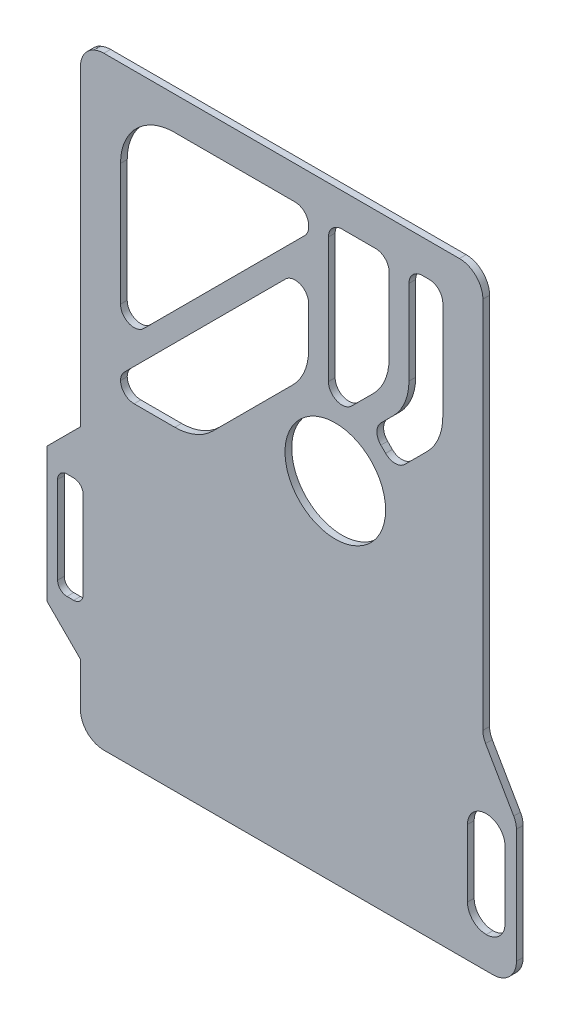
SolidWorks part; units mm, degrees
ref_plane "前视基准面" through (0, 0, 0) normal (0, 0, 1) x (1, 0, 0)
ref_plane "上视基准面" through (0, 0, 0) normal (0, 1, 0) x (1, 0, 0)
ref_plane "右视基准面" through (0, 0, 0) normal (1, 0, 0) x (0, 0, -1)
sketch "草图1" plane through (0, 0, 0) normal (0, 0, 1) x (1, 0, 0)
  line L27 (-1, -50) -> (-1.032, -50)
  line L28 (-34, 37.6372) -> (-34, 37.6623)
  line L29 (-36, 34.5) -> (-36, -12)
  line L30 (-36, -12) -> (-41, -17)
  line L31 (-41, -17) -> (-41, -37)
  line L32 (-41, -37) -> (-36, -42)
  line L33 (-36, -42) -> (-36, -48.5)
  line L34 (-32.5, -52) -> (-3, -52)
  line L35 (-38, -34.5) -> (-37, -34.5)
  line L36 (-36, -33.5) -> (-36, -20.5)
  line L37 (-37, -19.5) -> (-38, -19.5)
  line L38 (-39, -20.5) -> (-39, -33.5)
  line L40 (24, 37.9774) -> (-32.5, 37.9774)
  line L50 (12.9774, 31) -> (12.9774, 18.3848)
  line L51 (16, 33.0226) -> (15, 33.0226)
  line L52 (18.0226, 16.3137) -> (18.0226, 31)
  line L53 (12.3592, 7.3271) -> (15.6729, 10.6408)
  line L54 (8.7916, 8.0342) -> (9.4987, 7.3271)
  line L55 (10.6408, 12.7439) -> (8.7916, 10.8947)
  line L56 (8, 33.0226) -> (3, 33.0226)
  line L57 (10.0226, 19.8137) -> (10.0226, 31)
  line L58 (4.4302, 10.8982) -> (7.6729, 14.1408)
  line L59 (0.9774, 31) -> (0.9774, 12.3284)
  line L60 (-5.4302, 22.3592) -> (-29.4302, -1.6408)
  line L61 (-1.9774, 14.9289) -> (-1.9774, 20.9289)
  line L62 (-16.2561, -2.6729) -> (-4.3271, 9.2561)
  line L63 (-28, -5.0226) -> (-21.9289, -5.0226)
  line L64 (-26.5698, 5.3982) -> (-2.5698, 29.3982)
  line L65 (-30.0226, 25) -> (-30.0226, 6.8284)
  line L66 (-4, 33.0226) -> (-22, 33.0226)
  line L67 (-1.9774, 30.8284) -> (-1.9774, 31)
  line L69 (24, -2) -> (24, -22)
  line L70 (24, -22) -> (29, -30.6603)
  line L71 (29, -30.6603) -> (29, -52)
  line L72 (29, -52) -> (-3, -52)
  line L73 (24, 37.9774) -> (24, -2)
  line L74 (-38, -34.9) -> (-37, -34.9)
  line L75 (-35.6, -33.5) -> (-35.6, -20.5)
  line L76 (-37, -19.1) -> (-38, -19.1)
  line L77 (-39.4, -20.5) -> (-39.4, -33.5)
  arc A13 (-34, 37.6623) -> (-36, 34.5) centre (-32.5, 34.5) ccw
  arc A14 (-36, -48.5) -> (-32.5, -52) centre (-32.5, -48.5) ccw
  circle A15 centre (2, 0) radius 7.5
  arc A16 (-39, -33.5) -> (-38, -34.5) centre (-38, -33.5) ccw
  arc A17 (-37, -34.5) -> (-36, -33.5) centre (-37, -33.5) ccw
  arc A18 (-36, -20.5) -> (-37, -19.5) centre (-37, -20.5) ccw
  arc A19 (-38, -19.5) -> (-39, -20.5) centre (-38, -20.5) ccw
  arc A21 (-32.5, 37.9774) -> (-34, 37.6372) centre (-32.5, 34.5) ccw
  arc A28 (15, 33.0226) -> (12.9774, 31) centre (15, 31) ccw
  arc A29 (18.0226, 31) -> (16, 33.0226) centre (16, 31) ccw
  arc A30 (15.6729, 10.6408) -> (18.0226, 16.3137) centre (10, 16.3137) ccw
  arc A31 (9.4987, 7.3271) -> (12.3592, 7.3271) centre (10.9289, 8.7574) ccw
  arc A32 (8.7916, 10.8947) -> (8.7916, 8.0342) centre (10.2218, 9.4645) ccw
  arc A33 (10.6408, 12.7439) -> (12.9774, 18.3848) centre (5, 18.3848) ccw
  arc A34 (10.0226, 31) -> (8, 33.0226) centre (8, 31) ccw
  arc A35 (7.6729, 14.1408) -> (10.0226, 19.8137) centre (2, 19.8137) ccw
  arc A36 (0.9774, 12.3284) -> (4.4302, 10.8982) centre (3, 12.3284) ccw
  arc A37 (3, 33.0226) -> (0.9774, 31) centre (3, 31) ccw
  arc A38 (-1.9774, 20.9289) -> (-5.4302, 22.3592) centre (-4, 20.9289) ccw
  arc A39 (-4.3271, 9.2561) -> (-1.9774, 14.9289) centre (-10, 14.9289) ccw
  arc A40 (-21.9289, -5.0226) -> (-16.2561, -2.6729) centre (-21.9289, 3) ccw
  arc A41 (-30.0223, -3.0355) -> (-28, -5.0226) centre (-28, -3) ccw
  arc A42 (-29.4302, -1.6408) -> (-30.0223, -3.0355) centre (-28, -3.0711) ccw
  arc A43 (-30.0226, 6.8284) -> (-26.5698, 5.3982) centre (-28, 6.8284) ccw
  arc A44 (-22, 33.0226) -> (-30.0226, 25) centre (-22, 25) ccw
  arc A45 (-1.9774, 31) -> (-4, 33.0226) centre (-4, 31) ccw
  arc A46 (-2.5698, 29.3982) -> (-1.9774, 30.8284) centre (-4, 30.8284) ccw
  arc A47 (-37, -34.9) -> (-35.6, -33.5) centre (-37, -33.5) ccw
  arc A48 (-35.6, -20.5) -> (-37, -19.1) centre (-37, -20.5) ccw
  arc A49 (-38, -19.1) -> (-39.4, -20.5) centre (-38, -20.5) ccw
  arc A50 (-39.4, -33.5) -> (-38, -34.9) centre (-38, -33.5) ccw
  dimension "D3" = 5
  dimension "D1" = 60
  dimension "D2" = 150
  dimension "D4" = 30
  dimension "D5" = 0.4
  dimension "D6" = 50
extrude "凸台-拉伸1" add sketch "草图1" along normal blind 1 contours L40 A21 L28 A13 L29 L30 L31 L32 L33 A14 L34 L72 L71 L70 L69 A46 L64 A43 L65 A44 L66 A45 L67 A42 L60 A38 L61 A39 L62 A40 L63 A41 A37 L56 A34 L57 A35 L58 A36 L59 region at (-4.9179, -14.8652, 0)
fillet "圆角1" radius 3 2 edges at (29, -30.6603, 0.5) (24, -22, 0.5)
fillet "圆角2" radius 3.5 2 edges at (29, -52, 0.5) (24, 37.9774, 0.5)
sketch "草图2" plane through (0, 0, 0) normal (0, 0, -1) x (-1, 0, 0)
  line L28 (-27.3, -44.51) -> (-27.3, -34.49)
  line L29 (-24.51, -31.7) -> (-24.49, -31.7)
  line L30 (-21.7, -44.51) -> (-21.7, -34.49)
  line L31 (-24.51, -47.3) -> (-24.49, -47.3)
  arc A18 (-24.51, -31.7) -> (-27.3, -34.49) centre (-24.51, -34.49) ccw
  arc A19 (-21.7, -34.49) -> (-24.49, -31.7) centre (-24.49, -34.49) ccw
  arc A20 (-24.49, -47.3) -> (-21.7, -44.51) centre (-24.49, -44.51) ccw
  arc A21 (-27.3, -44.51) -> (-24.51, -47.3) centre (-24.51, -44.51) ccw
  point P10 (-27, -47)
  point P13 (-22, -47)
  point P16 (-22, -32)
  dimension "D1" = 5
  dimension "D2" = 15
extrude "切除-拉伸1" cut sketch "草图2" against normal blind 10 contours L28 A18 L29 A19 L30 A20 L31 A21
sketch "草图4" plane through (0, 0, 0) normal (0, 0, -1) x (-1, 0, 0)
  line L0 (-24, 34.4774) -> (-24, -21.1962) construction
  line L1 (-22, -27) -> (-21.6, -27)
  line L2 (-22, -27) -> (-22, -2)
  line L3 (-22, -2) -> (-21.6, -2)
  line L4 (-21.6, -27) -> (-21.6, -2)
  line L5 (32.5, -52) -> (-25.5, -52) construction
  dimension "D1" = 2
  dimension "D2" = 0.4
  dimension "D3" = 25
  dimension "D4" = 25
extrude "凸台-拉伸2" [suppressed] add sketch "草图4" along normal blind 1.6
